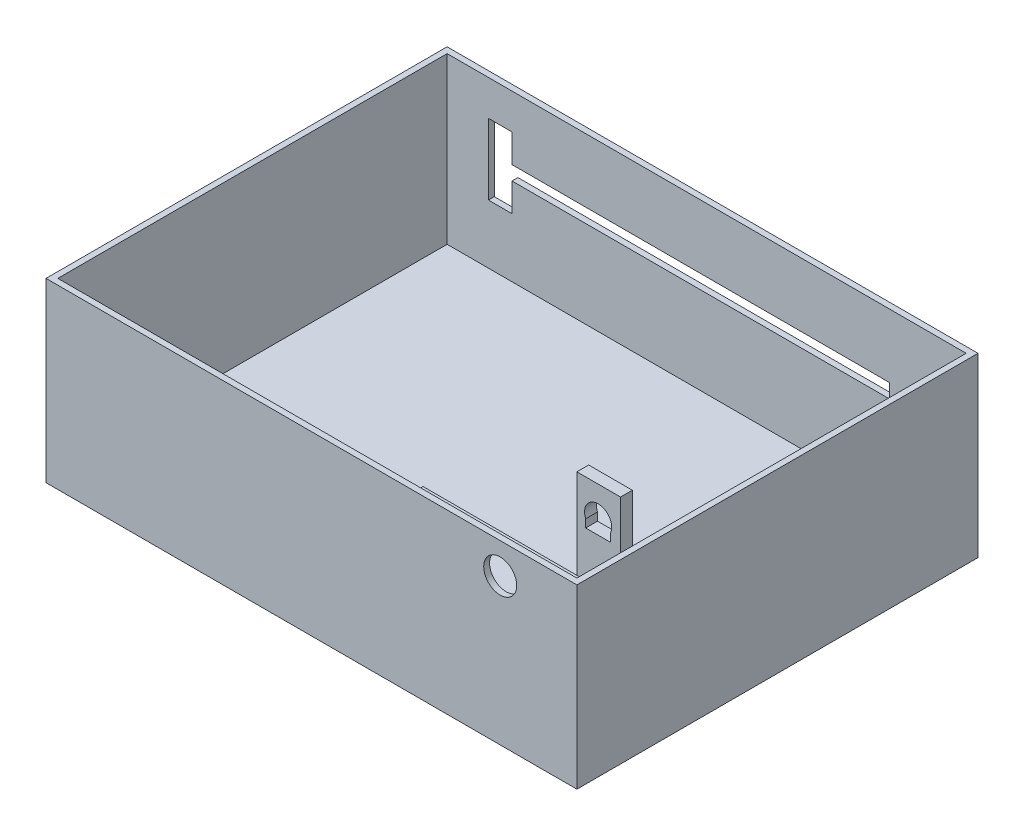
SolidWorks part; units mm, degrees
note: The reader was unsure of these and kept them because the rebuilt part matched: shared geometry of "Sketch6<4>".
ref_plane "Front Plane" through (0, 0, 0) normal (0, 0, 1) x (1, 0, 0)
ref_plane "Top Plane" through (0, 0, 0) normal (0, 1, 0) x (1, 0, 0)
ref_plane "Right Plane" through (0, 0, 0) normal (1, 0, 0) x (0, 0, -1)
sketch "Sketch1" plane through (0, 0, 0) normal (0, 1, 0) x (1, 0, 0)
  line L1 (-112.5, -85) -> (112.5, -85)
  line L2 (-112.5, -85) -> (-112.5, 85)
  line L3 (-112.5, 85) -> (112.5, 85)
  line L4 (112.5, -85) -> (112.5, 85)
  line L5 (-112.5, -85) -> (112.5, 85) construction
  line L6 (-112.5, 85) -> (112.5, -85) construction
  point P0 (0, 0)
  point P6 (0, 0)
  dimension "D1" = 225
  dimension "D2" = 170
extrude "Boss-Extrude1" add sketch "Sketch1" along normal blind 75
sketch "Sketch2" plane through (0, 75, 0) normal (0, 1, 0) x (1, 0, 0)
  line L1 (110, -82.5) -> (-110, -82.5)
  line L2 (110, -82.5) -> (110, 82.5)
  line L3 (110, 82.5) -> (-110, 82.5)
  line L4 (-110, -82.5) -> (-110, 82.5)
  line L5 (110, -82.5) -> (-110, 82.5) construction
  line L6 (110, 82.5) -> (-110, -82.5) construction
  point P0 (0, 0)
  dimension "D1" = 220
  dimension "D2" = 165
extrude "Cut-Extrude1" cut sketch "Sketch2" against normal blind 70
sketch "Sketch5" plane through (0, 0, -85) normal (0, 0, -1) x (-1, 0, 0)
  line L0 (92.5, 60) -> (92.5, 30)
  line L1 (92.5, 30) -> (82.5, 30)
  line L2 (82.5, 30) -> (82.5, 42)
  line L3 (82.5, 42) -> (-77.5, 42)
  line L4 (-77.5, 42) -> (-77.5, 48)
  line L5 (-77.5, 48) -> (82.5, 48)
  line L6 (82.5, 48) -> (82.5, 60)
  line L7 (82.5, 60) -> (92.5, 60)
  line L9 (-112.5, 75) -> (112.5, 75) construction
  line L10 (112.5, 75) -> (112.5, 0) construction
  point P10 (-77.5, 45)
  dimension "D1" = 30
  dimension "D2" = 10
  dimension "D3" = 160
  dimension "D4" = 20
  dimension "D5" = 6
  dimension "D6" = 12
  dimension "D7" = 12
  dimension "D8" = 30
extrude "Cut-Extrude2" cut sketch "Sketch5" against normal blind 10
sketch "Sketch6" plane through (0, 5, 0) normal (0, 1, 0) x (1, 0, 0)
  line L1 (-85, 17.5) -> (8.2, 17.5)
  line L2 (-85, 17.5) -> (-85, -68.7)
  line L3 (-85, -68.7) -> (8.2, -68.7)
  line L4 (8.2, 17.5) -> (8.2, -68.7)
  line L5 (110, -82.5) -> (110, 82.5) construction
  line L6 (-110, -82.5) -> (110, -82.5) construction
  line L7 (-110, 82.5) -> (-110, -82.5) construction
  line L9 (22.8105, -60.5) -> (94.8105, -60.5)
  line L10 (22.8105, -60.5) -> (22.8105, -82.5)
  line L11 (22.8105, -82.5) -> (94.8105, -82.5)
  line L12 (94.8105, -60.5) -> (94.8105, -82.5)
  line L13 (71, -43.5) -> (76, -43.5)
  line L14 (71, -43.5) -> (71, -38.5)
  line L15 (71, -38.5) -> (76, -38.5)
  line L16 (76, -43.5) -> (76, -38.5)
  line L17 (84.5, -43.5) -> (89.5, -43.5)
  line L18 (84.5, -43.5) -> (84.5, -38.5)
  line L19 (84.5, -38.5) -> (89.5, -38.5)
  line L20 (89.5, -43.5) -> (89.5, -38.5)
  line M10 (-110, -82.5) -> (110, -82.5)
  dimension "D1" = 93.2
  dimension "D2" = 86.2
  dimension "D3" = 100
  dimension "D4" = 25
  dimension "D5" = 72
  dimension "D6" = 22
  dimension "D7" = 22
  dimension "D8" = 17
  dimension "D9" = 17
  dimension "D10" = 34
  dimension "D11" = 5
  dimension "D12" = 15.1895
  dimension "D13" = 13.5
extrude "Boss-Extrude2" add sketch "Sketch6" along normal blind 49 contours L12 L9 L10 M10 | L14 L13 L16 L15
sketch "Sketch8" plane through (0, 0, 82.5) normal (0, 0, -1) x (-1, 0, 0)
  line L0 (-110, 5) -> (-110, 75) construction
  line L1 (110, 75) -> (-110, 75) construction
  circle A0 centre (-80, 62) radius 7
  dimension "D3" = 14
  dimension "D1" = 30
  dimension "D2" = 13
extrude "Cut-Extrude3" cut sketch "Sketch8" against normal blind 25
extrude "Boss-Extrude4" add sketch "Sketch6<4>" along normal blind 70 contours L13 L16 L15 L14 | L17 L20 L19 L18
sketch "Sketch6<4>" plane through (0, 5, 0) normal (0, 1, 0) x (1, 0, 0) same geometry as "Sketch6"
sketch "Sketch11" plane through (0, 5, 0) normal (0, 1, 0) x (1, 0, 0)
  line L5 (76, -38.5) -> (84.5, -38.5)
  line L6 (76, -38.5) -> (76, -43.5)
  line L7 (76, -43.5) -> (84.5, -43.5)
  line L8 (84.5, -38.5) -> (84.5, -43.5)
extrude "Boss-Extrude5" add sketch "Sketch11" along normal blind 40 and the other way blind 1 from offset 30
sketch "Sketch12" plane through (0, 0, 43.5) normal (0, 0, 1) x (1, 0, 0)
  line L0 (110, 75) -> (-110, 75) construction
  line L2 (110, 5) -> (110, 75) construction
  line L3 (74.75, 59.6548) -> (74.75, 56.25)
  line L4 (74.75, 56.25) -> (85.25, 56.25)
  line L5 (85.25, 56.25) -> (85.25, 59.6548)
  arc A0 (85.25, 59.6548) -> (74.75, 59.6548) centre (80, 62) ccw
  dimension "D3" = 11.5
  dimension "D1" = 13
  dimension "D2" = 30
  dimension "D4" = 10.5
extrude "Cut-Extrude4" cut sketch "Sketch12" against normal blind 10
sketch "Sketch13" plane through (0, 54, 0) normal (0, 1, 0) x (1, 0, 0)
  line L0 (22.8105, -60.5) -> (22.8105, -82.5) construction
  line L1 (25.3105, -80) -> (92.3105, -80)
  line L2 (25.3105, -80) -> (25.3105, -63)
  line L3 (25.3105, -63) -> (92.3105, -63)
  line L4 (92.3105, -80) -> (92.3105, -63)
  line L5 (22.8105, -60.5) -> (94.8105, -60.5) construction
  line L6 (-110, -82.5) -> (110, -82.5) construction
  line L7 (94.8105, -60.5) -> (94.8105, -82.5) construction
  dimension "D1" = 2.5
  dimension "D2" = 2.5
  dimension "D3" = 2.5
  dimension "D4" = 2.5
extrude "Cut-Extrude5" cut sketch "Sketch13" against normal blind 42.5 from offset 2.5 offset against normal yes
fillet "Fillet1" radius 17 8 edges at (71, 5, 41) (84.5, 5, 41) (73.5, 5, 38.5) (87, 5, 38.5) (87, 5, 43.5) (89.5, 5, 41) (76, 5, 41) (73.5, 5, 43.5)
